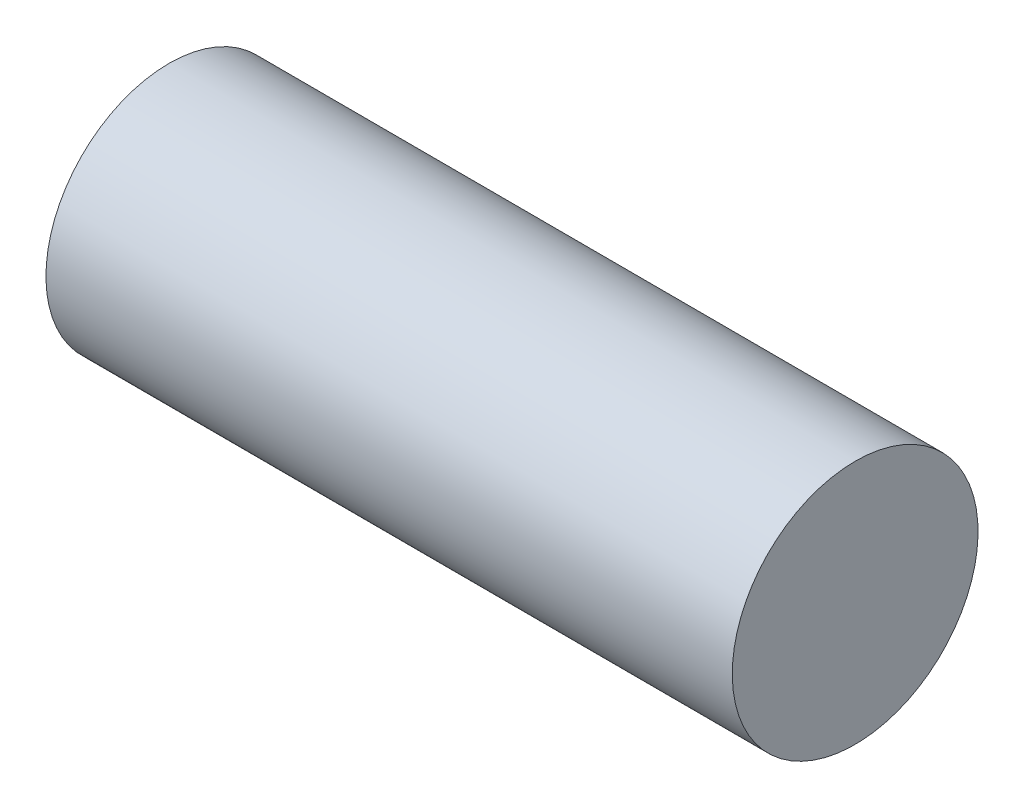
SolidWorks part; units mm, degrees
ref_plane "X-Y Datum" through (0, 0, 0) normal (0, 0, 1) x (1, 0, 0)
ref_plane "X-Z Datum" through (0, 0, 0) normal (0, 1, 0) x (1, 0, 0)
ref_plane "Y-Z Datum" through (0, 0, 0) normal (1, 0, 0) x (0, 0, -1)
sketch3d "3DSketch1"
  line L0 (29.0347, 200.8567, 163.3218) -> (11.5347, 200.8445, 163.3218) construction
  line L1 (-13.6473, 200.895, 163.3218) -> (-6.7095, 200.8998, 163.3218) construction
  line L2 (-13.558, 200.8951, 163.3218) -> (12.6858, 200.8453, 163.3218)
  point P0 (12.6858, 200.8453, 163.3218)
  point P1 (-13.558, 200.8951, 163.3218)
sweep "Sweep1" add path "3DSketch1" circular profile diameter 9.398 parameters "D3"=9.398
